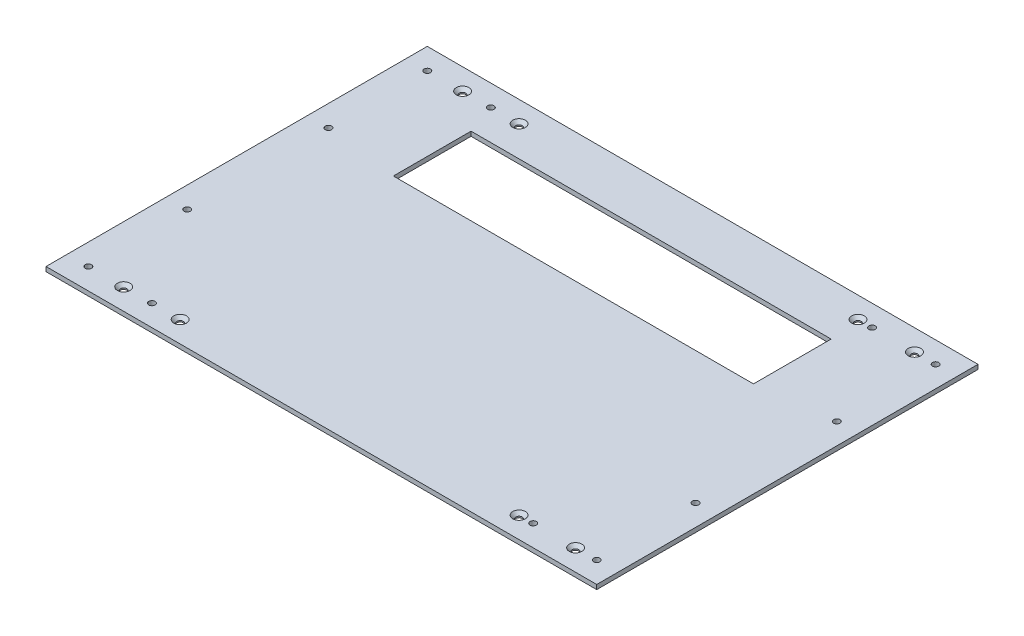
SolidWorks part; units mm, degrees
ref_plane "Front Plane" through (0, 0, 0) normal (0, 0, 1) x (1, 0, 0)
ref_plane "Top Plane" through (0, 0, 0) normal (0, 1, 0) x (1, 0, 0)
ref_plane "Right Plane" through (0, 0, 0) normal (1, 0, 0) x (0, 0, -1)
sketch "Sketch1" plane through (0, 0, 0) normal (0, 1, 0) x (1, 0, 0)
  line L1 (-195, -135) -> (195, -135)
  line L2 (-195, -135) -> (-195, 135)
  line L3 (-195, 135) -> (195, 135)
  line L4 (195, -135) -> (195, 135)
  line L5 (-195, -135) -> (195, 135) construction
  line L6 (-195, 135) -> (195, -135) construction
  point P0 (0, 0)
  dimension "D1" = 390
  dimension "D2" = 270
extrude "Boss-Extrude1" add sketch "Sketch1" along normal blind 3.175
hole_wizard "CSK for M4 SFHCS2" positions "Sketch4" profile "Sketch6" countersink size "M4" standard "ANSI Metric" end condition through all
sketch "Sketch4" plane through (0, 3.175, 0) normal (0, 1, 0) x (1, 0, 0)
  line L0 (-155, 120) -> (-115, 120)
  line L2 (125, 120) -> (165, 120)
  line L4 (195, 135) -> (-195, 135) construction
  point P1 (-155, 120)
  point P2 (-115, 120)
  point P5 (125, 120)
  point P6 (165, 120)
  point P11 (-135, 120)
  point P13 (145, 120)
  dimension "D1" = 40
  dimension "D2" = 40
  dimension "D3" = 15
  dimension "D4" = 60
  dimension "D5" = 50
sketch "Sketch6" plane through (-155, 3.175, -120) normal (1, 0, 0) x (0, 0, 1)
  line L0 (0, 0) -> (0, 3.175)
  line L1 (0, 3.175) -> (2.25, 3.175)
  line L2 (2.25, 3.175) -> (2.25, 2.23)
  line L3 (2.25, 2.23) -> (4.48, 0)
  line L5 (4.48, 0) -> (0, 0)
  line L6 (-2.25, 2.23) -> (-4.48, 0) construction
  line L11 (0, -6.35) -> (0, 107.95) construction
  dimension "Thru Hole Dia." = 4.5
  dimension "Thru Hole Depth" = 3.175
  dimension "Near C'Sink Dia." = 8.96
  dimension "Near C'Sink Angle" = 90
mirror "Mirror2" about plane through (0, 0, 0) normal (0, 0, 1) of "CSK for M4 SFHCS2"
hole_wizard "M4 Clearance Hole1" positions "Sketch7" profile "Sketch9" hole size "M4" standard "ANSI Metric" end condition through all
sketch "Sketch7" plane through (0, 3.175, 0) normal (0, 1, 0) x (1, 0, 0)
  line L0 (-195, 135) -> (-195, -135) construction
  line L1 (195, 135) -> (-195, 135) construction
  point P0 (-180, 120)
  point P2 (-180, 50)
  point P4 (-135, 120)
  dimension "D1" = 15
  dimension "D2" = 15
  dimension "D3" = 45
  dimension "D4" = 70
sketch "Sketch9" plane through (-180, 3.175, -120) normal (1, 0, 0) x (0, 0, 1)
  line L0 (0, 0) -> (0, 3.175)
  line L1 (0, 3.175) -> (2.25, 3.175)
  line L2 (2.25, 3.175) -> (2.25, 0)
  line L5 (2.25, 0) -> (0, 0)
  line L11 (0, -6.35) -> (0, 107.95) construction
  dimension "Thru Hole Dia." = 4.5
  dimension "Thru Hole Depth" = 3.175
mirror "Mirror3" about plane through (0, 0, 0) normal (1, 0, 0) of "M4 Clearance Hole1" second plane through (0, 0, 0) second plane normal (0, 0, 1)
sketch "Sketch10" plane through (0, 3.175, 0) normal (0, 1, 0) x (1, 0, 0)
  line L0 (195, 135) -> (-195, 135) construction
  line L1 (-127.5, 43.5) -> (127.5, 43.5)
  line L2 (-127.5, 43.5) -> (-127.5, 98.5)
  line L3 (-127.5, 98.5) -> (127.5, 98.5)
  line L4 (127.5, 43.5) -> (127.5, 98.5)
  line L5 (-127.5, 43.5) -> (127.5, 98.5) construction
  line L6 (-127.5, 98.5) -> (127.5, 43.5) construction
  point P0 (0, 71)
  point P7 (0, 0)
  dimension "D1" = 255
  dimension "D2" = 55
  dimension "D3" = 64
extrude "Cut-Extrude1" cut sketch "Sketch10" against normal blind 3.175
